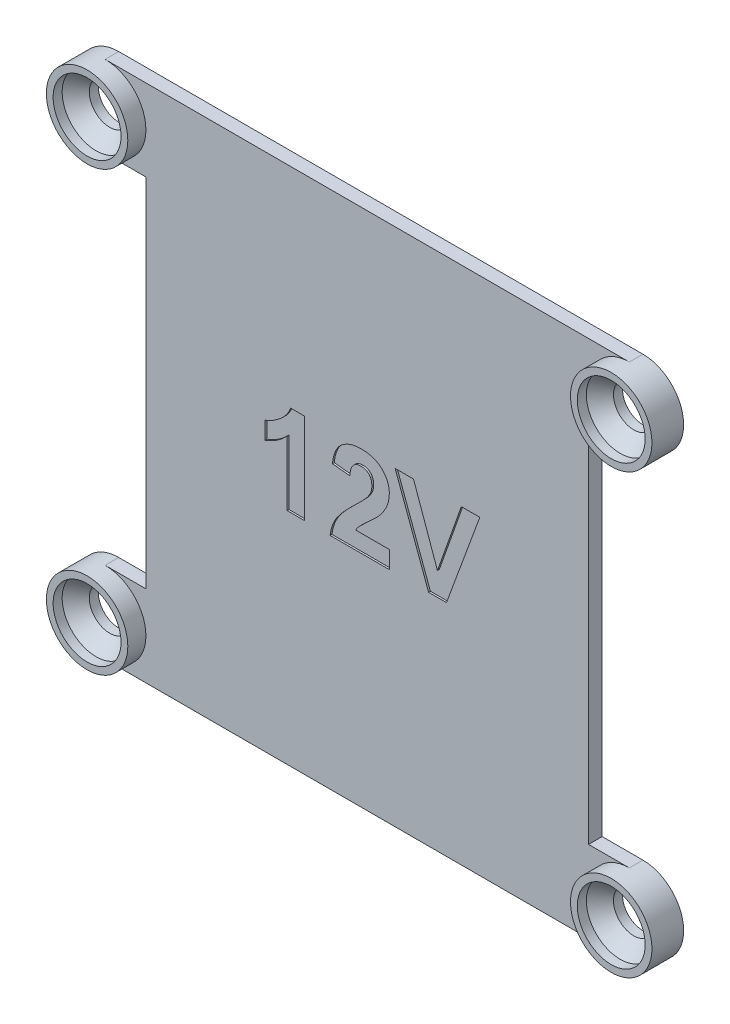
SolidWorks part; units mm, degrees
ref_plane "Front Plane" through (0, 0, 0) normal (0, 0, 1) x (1, 0, 0)
ref_plane "Top Plane" through (0, 0, 0) normal (0, 1, 0) x (1, 0, 0)
ref_plane "Right Plane" through (0, 0, 0) normal (1, 0, 0) x (0, 0, -1)
sketch "Sketch1" plane through (0, 0, 0) normal (0, 0, 1) x (1, 0, 0)
  line L0 (-20.75, 28.7) -> (20.75, 28.7)
  line L1 (-20.75, -28.7) -> (20.75, -28.7)
  line L10 (-22.95, 16.6) -> (-20.75, 16.6)
  line L11 (-20.75, 16.6) -> (-20.75, 28.7)
  line L12 (-20.75, 28.7) -> (-28.95, 28.7)
  line L13 (-28.95, 19.7) -> (-24.45, 19.7)
  line L14 (-24.45, 19.7) -> (-24.45, -19.7)
  line L15 (-24.45, -19.7) -> (-28.95, -19.7)
  line L16 (-28.95, -28.7) -> (-20.75, -28.7)
  line L17 (-20.75, -28.7) -> (-20.75, -16.6)
  line L18 (-20.75, -16.6) -> (-22.95, -16.6)
  line L19 (-22.95, -16.6) -> (-22.95, 16.6)
  line L20 (-22.95, 16.6) -> (-20.75, 16.6)
  line L21 (-20.75, 16.6) -> (-20.75, 28.7)
  line L22 (-20.75, 28.7) -> (-28.95, 28.7)
  line L23 (-28.95, 19.7) -> (-24.45, 19.7)
  line L24 (-24.45, 19.7) -> (-24.45, -19.7)
  line L25 (-24.45, -19.7) -> (-28.95, -19.7)
  line L26 (-28.95, -28.7) -> (-20.75, -28.7)
  line L27 (-20.75, -28.7) -> (-20.75, -16.6)
  line L28 (-20.75, -16.6) -> (-22.95, -16.6)
  line L29 (-22.95, -16.6) -> (-22.95, 16.6)
  line L30 (20.75, 28.7) -> (20.75, 16.6)
  line L31 (20.75, 16.6) -> (22.95, 16.6)
  line L32 (22.95, 16.6) -> (22.95, -16.6)
  line L33 (22.95, -16.6) -> (20.75, -16.6)
  line L34 (20.75, -16.6) -> (20.75, -28.7)
  line L35 (20.75, -28.7) -> (28.95, -28.7)
  line L36 (28.95, -19.7) -> (24.45, -19.7)
  line L37 (24.45, -19.7) -> (24.45, 19.7)
  line L38 (24.45, 19.7) -> (28.95, 19.7)
  line L39 (28.95, 28.7) -> (20.75, 28.7)
  line L40 (20.75, 28.7) -> (20.75, 16.6)
  line L41 (20.75, 16.6) -> (22.95, 16.6)
  line L42 (22.95, 16.6) -> (22.95, -16.6)
  line L43 (22.95, -16.6) -> (20.75, -16.6)
  line L44 (20.75, -16.6) -> (20.75, -28.7)
  line L45 (20.75, -28.7) -> (28.95, -28.7)
  line L46 (28.95, -19.7) -> (24.45, -19.7)
  line L47 (24.45, -19.7) -> (24.45, 19.7)
  line L48 (24.45, 19.7) -> (28.95, 19.7)
  line L49 (28.95, 28.7) -> (20.75, 28.7)
  circle A0 centre (28.95, 24.2) radius 2.25 construction
  circle A1 centre (28.95, -24.2) radius 2.25 construction
  arc A2 (-28.95, 28.7) -> (-28.95, 19.7) centre (-28.95, 24.2) ccw
  arc A3 (-28.95, -19.7) -> (-28.95, -28.7) centre (-28.95, -24.2) ccw
  arc A4 (-28.95, 28.7) -> (-28.95, 19.7) centre (-28.95, 24.2) ccw
  arc A5 (-28.95, -19.7) -> (-28.95, -28.7) centre (-28.95, -24.2) ccw
  arc A6 (28.95, -28.7) -> (28.95, -19.7) centre (28.95, -24.2) ccw
  arc A7 (28.95, 19.7) -> (28.95, 28.7) centre (28.95, 24.2) ccw
  arc A8 (28.95, -28.7) -> (28.95, -19.7) centre (28.95, -24.2) ccw
  arc A9 (28.95, 19.7) -> (28.95, 28.7) centre (28.95, 24.2) ccw
  circle A10 centre (-28.95, -24.2) radius 2.25 construction
  circle A11 centre (-28.95, 24.2) radius 2.25 construction
  circle A12 centre (28.95, 24.2) radius 2.25
  circle A13 centre (28.95, -24.2) radius 2.25
  circle A14 centre (-28.95, -24.2) radius 2.25
  circle A15 centre (-28.95, 24.2) radius 2.25
  dimension "D1" = 0
  dimension "D2" = 0
extrude "Boss-Extrude1" add sketch "Sketch1" along normal blind 1.5 contours L25 A5 L26 L27 L28 L29 L20 L21 L22 A4 L23 L24 | L44 L43 L42 L41 L40 L0 L21 L20 L29 L28 L27 L1 | L48 A9 L49 L40 L41 L42 L43 L44 L45 A8 L46 L47 region at (0, 0, 0) region at (-21.3379, 22.65, 0) region at (24.85, 28.1121, 0)
sketch "Sketch2" plane through (0, 0, 1.5) normal (0, 0, 1) x (1, 0, 0)
  circle A0 centre (-28.95, 24.2) radius 4.5
  arc A1 (-28.95, 28.7) -> (-28.95, 19.7) centre (-28.95, 24.2) ccw construction
  circle A2 centre (-28.95, 24.2) radius 2.25 construction
  circle A3 centre (-28.95, 24.2) radius 2.25
  circle A4 centre (28.95, 24.2) radius 2.25 construction
  circle A5 centre (28.95, 24.2) radius 2.25
  circle A6 centre (28.95, 24.2) radius 4.5
  arc A7 (28.95, 19.7) -> (28.95, 28.7) centre (28.95, 24.2) ccw construction
  circle A8 centre (28.95, -24.2) radius 2.25 construction
  circle A9 centre (-28.95, -24.2) radius 2.25 construction
  circle A10 centre (28.95, -24.2) radius 2.25
  circle A11 centre (-28.95, -24.2) radius 2.25
  circle A12 centre (-28.95, -24.2) radius 4.5
  arc A13 (-28.95, -19.7) -> (-28.95, -28.7) centre (-28.95, -24.2) ccw construction
  circle A14 centre (28.95, -24.2) radius 4.5
  arc A15 (28.95, -28.7) -> (28.95, -19.7) centre (28.95, -24.2) ccw construction
extrude "Boss-Extrude2" add sketch "Sketch2" along normal blind 1
chamfer "Chamfer1" distance 1.5 angle 45 4 edges at (-26.7, -24.2, 2.5) (31.2, -24.2, 2.5) (31.2, 24.2, 2.5) (-26.7, 24.2, 2.5)
sketch "Sketch3" plane through (0, 0, 2.5) normal (0, 0, 1) x (1, 0, 0)
  circle A0 centre (-28.95, -24.2) radius 4.5 construction
  circle A1 centre (28.95, -24.2) radius 4.5 construction
  circle A2 centre (28.95, 24.2) radius 4.5 construction
  circle A3 centre (-28.95, 24.2) radius 4.5 construction
  circle A4 centre (-28.95, -24.2) radius 4.5
  circle A5 centre (28.95, -24.2) radius 4.5
  circle A6 centre (28.95, 24.2) radius 4.5
  circle A7 centre (-28.95, 24.2) radius 4.5
  circle A8 centre (-28.95, -24.2) radius 3.75 construction
  circle A9 centre (28.95, -24.2) radius 3.75 construction
  circle A10 centre (28.95, 24.2) radius 3.75 construction
  circle A11 centre (-28.95, 24.2) radius 3.75 construction
  circle A12 centre (-28.95, -24.2) radius 3.75
  circle A13 centre (28.95, -24.2) radius 3.75
  circle A14 centre (28.95, 24.2) radius 3.75
  circle A15 centre (-28.95, 24.2) radius 3.75
extrude "Boss-Extrude3" add sketch "Sketch3" along normal blind 1
sketch "Sketch4" plane through (0, 0, 1.5) normal (0, 0, 1) x (1, 0, 0)
  line L0 (-24.45, -4.4145) -> (24.45, -4.4145) construction
  line L1 (-24.45, 19.7) -> (-24.45, -19.7) construction
  line L2 (24.45, -19.7) -> (24.45, 19.7) construction
  text T0 "12V" font "Arial" height 10
extrude "Cut-Extrude1" cut sketch "Sketch4" against normal blind 0.2
